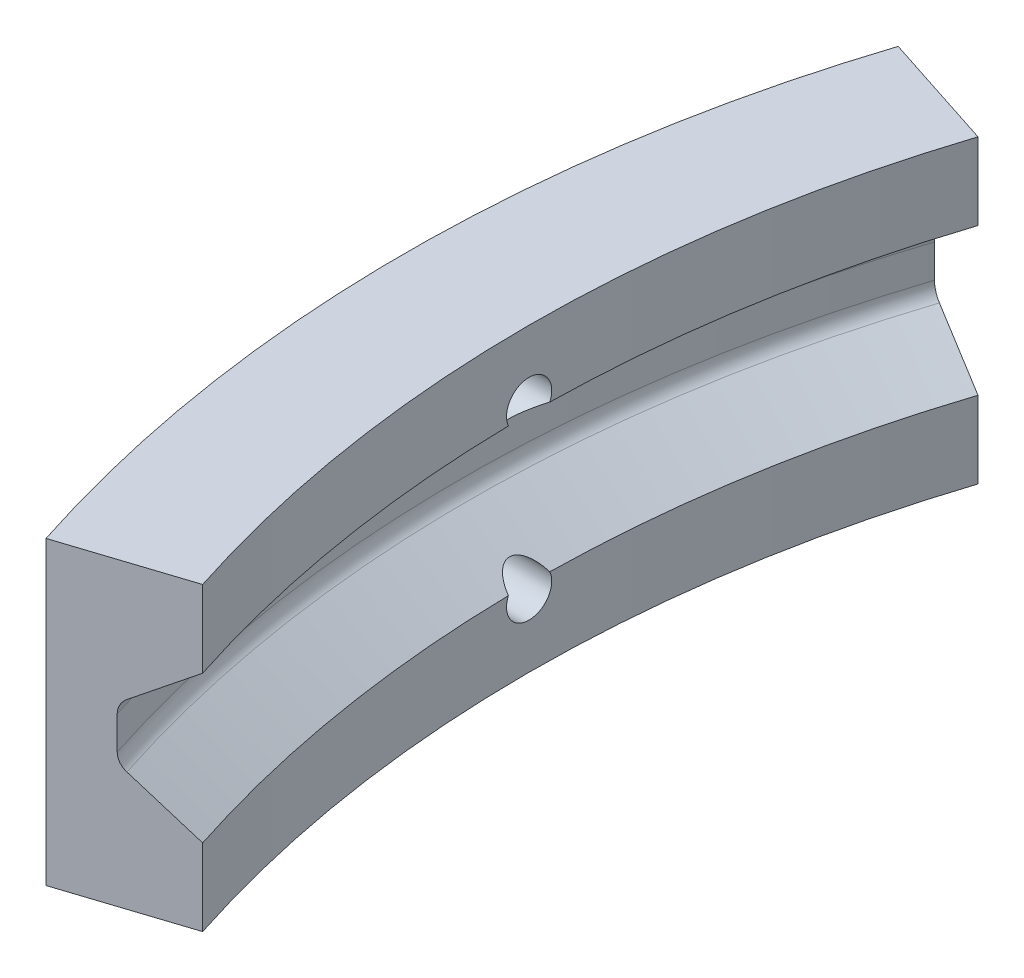
SolidWorks part; units mm, degrees
material "6061-T6 (SS)"
ref_plane "Ebene vorne" through (0, 0, 0) normal (0, 0, 1) x (1, 0, 0)
ref_plane "Ebene oben" through (0, 0, 0) normal (0, 1, 0) x (1, 0, 0)
ref_plane "Ebene rechts" through (0, 0, 0) normal (1, 0, 0) x (0, 0, -1)
sketch "Skizze2" plane through (0, 0, 0) normal (0, 0, 1) x (1, 0, 0)
  line L0 (-55.5, 3.2505) -> (-58.1589, 1.3888)
  line L2 (-61, -6.65) -> (-61, 6.65)
  line L3 (-61, 6.65) -> (-55.5, 6.65)
  line L5 (-58.5, 0.7334) -> (-58.5, -0.7334)
  line L7 (-55.5, 3.2505) -> (-55.5, 6.65)
  line L8 (-58.5, 0) -> (-61, 0) construction
  line L9 (55, 0) -> (-55, 0) construction
  line L10 (-55.5, -3.2505) -> (-55.5, -6.65)
  line L11 (-61, -6.65) -> (-55.5, -6.65)
  line L12 (-55.5, -3.2505) -> (-58.1589, -1.3888)
  line L13 (-58, 1.5) -> (-58, -1.5) construction
  line L14 (-55, 6.65) -> (-55, -6.65) construction
  arc A0 (-58.1589, -1.3888) -> (-58.5, -0.7334) centre (-57.7, -0.7334) cw
  arc A1 (-58.1589, 1.3888) -> (-58.5, 0.7334) centre (-57.7, 0.7334) ccw
  point P0 (-58, 1.5)
  point P11 (-58, -1.5)
  point P22 (-58.5, -1.1499)
  point P25 (-58.5, 1.1499)
  dimension "D12" = 0.8
  dimension "D1" = 61
  dimension "D2" = 2.5
  dimension "D3" = 13.3
  dimension "D4" = 3
  dimension "D5" = 3
  dimension "D6" = 35
  dimension "D7" = 3
  dimension "D8" = 3.3995
  dimension "D9" = 0.5
  dimension "D10" = 5.5
  dimension "D11" = 2.2998
ref_axis "Achse1" through (0, 6.7079, 0) along (0, -1, 0)
revolve "Rotation2" add sketch "Skizze2" angle 36 mid plane about axis through (0, 6.7079, 0) along (0, -1, 0)
ref_axis "Achse2" through (-60.5098, 0, 0) along (1, 0, 0)
ref_plane "Ebene1" through (-58.0144, 0, 0) normal (1, 0, 0) x (0, 0, -1)
sketch "Skizze3" plane through (-58.0144, 0, 0) normal (1, 0, 0) x (0, 0, -1)
  line L0 (0, 6.7079) -> (0, -6.7079) construction
  line L1 (18.85, 6.65) -> (-18.85, 6.65) construction
  line L2 (-18.85, -6.65) -> (18.85, -6.65) construction
  circle A1 centre (0, 3.65) radius 1
  circle A2 centre (0, -3.65) radius 1
  dimension "D1" = 2
  dimension "D2" = 2
  dimension "D3" = 3
  dimension "D4" = 3
  dimension "D5" = 7.3
extrude "Schnitt-Linear austragen2" cut sketch "Skizze3" along normal blind 3.4 and the other way through all
